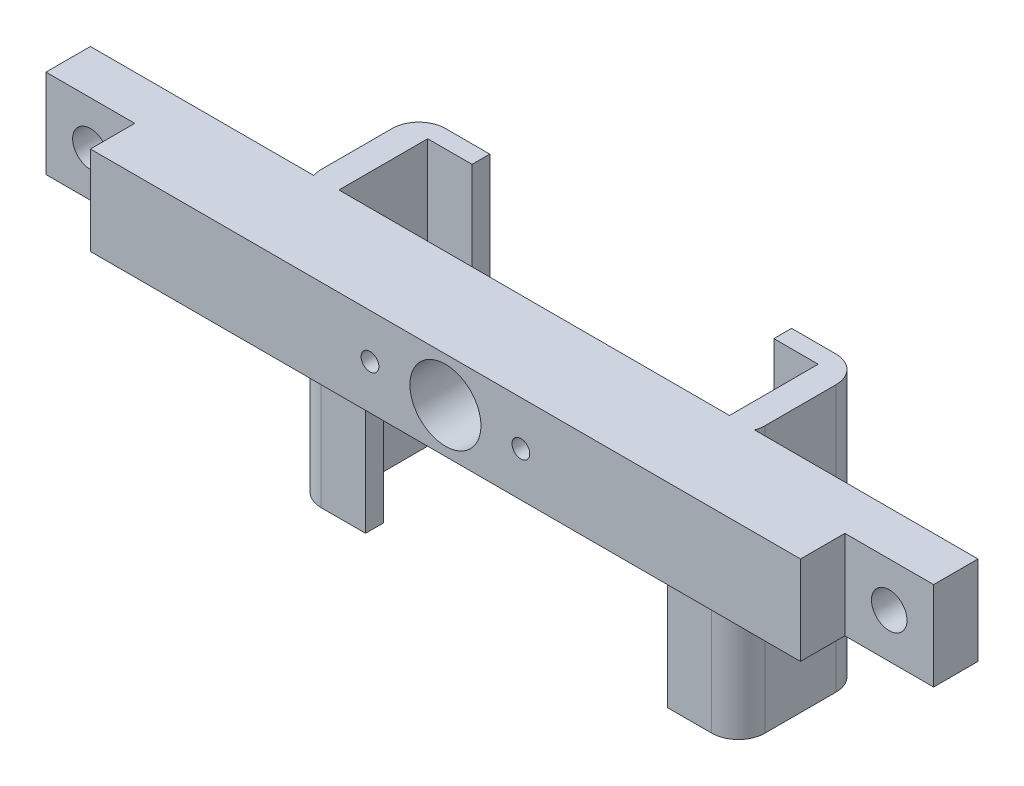
SolidWorks part; units mm, degrees
ref_plane "Front Plane" through (0, 0, 0) normal (0, 0, 1) x (1, 0, 0)
ref_plane "Top Plane" through (0, 0, 0) normal (0, 1, 0) x (1, 0, 0)
ref_plane "Right Plane" through (0, 0, 0) normal (1, 0, 0) x (0, 0, -1)
sketch "Sketch1" plane through (0, 0, 0) normal (0, 0, 1) x (1, 0, 0)
  line L1 (-50, 5) -> (50, 5)
  line L2 (-50, 5) -> (-50, -5)
  line L3 (-50, -5) -> (50, -5)
  line L4 (50, 5) -> (50, -5)
  line L5 (-50, 5) -> (50, -5) construction
  line L6 (-50, -5) -> (50, 5) construction
  point P0 (0, 0)
  dimension "D1" = 100
  dimension "D2" = 10
extrude "Boss-Extrude1" add sketch "Sketch1" along normal blind 10
sketch "Sketch2" plane through (0, 5, 0) normal (0, 1, 0) x (1, 0, 0)
  line L5 (-50, -10) -> (-40, -10)
  line L6 (-50, -10) -> (-50, -5)
  line L7 (-50, -5) -> (-40, -5)
  line L8 (-40, -10) -> (-40, -5)
  dimension "D1" = 10
  dimension "D2" = 5
sketch "Sketch6" plane through (0, 0, 0) normal (0, 0, -1) x (-1, 0, 0)
  line L0 (0, 5) -> (0, -5) construction
  line L1 (-25, 5) -> (-25, -5)
  line L3 (-25, 5) -> (-22, 5)
  line L4 (-50, 5) -> (-50, -5)
  line L5 (-50, -5) -> (50, -5)
  line L6 (-50, 5) -> (-50, -5)
  line L7 (50, 5) -> (-50, 5)
  line L9 (-50, -5) -> (50, -5)
  line L11 (50, 5) -> (-50, 5)
  line L12 (-22, 5) -> (-22, -5)
  line L13 (-22, -5) -> (-25, -5)
  line L17 (50, -5) -> (50, 5)
  line L18 (50, -5) -> (50, 5)
  line M11 (-50, -5) -> (50, -5)
  line M13 (50, 5) -> (-50, 5)
  dimension "D2" = 25
  dimension "D3" = 3
  dimension "D1" = 0
extrude "Boss-Extrude2" add sketch "Sketch6" along normal blind 12 contours L12 L1 M13 M11 region at (23.5, 0, 0)
sketch "Sketch8" plane through (22, 0, 0) normal (-1, 0, 0) x (0, 0, 1)
  line L0 (-12, -5) -> (0, -5) construction
  line L1 (-12, 5) -> (-10, 5)
  line L2 (-12, 5) -> (-12, -5)
  line L3 (-12, -5) -> (-10, -5)
  line L4 (-10, 5) -> (-10, -5)
  dimension "D1" = 2
extrude "Boss-Extrude3" add sketch "Sketch8" along normal blind 5
sketch "Sketch9" plane through (0, -5, 0) normal (0, -1, 0) x (1, 0, 0)
  line L0 (17, -12) -> (17, 0) construction
  line L1 (-50, 0) -> (22, 0) construction
  line L2 (17, 0) -> (22, 0)
  line L4 (17, 0) -> (17, 2)
  line L5 (17, 2) -> (25, 2)
  line L6 (25, 0) -> (25, 2)
  line L7 (22, 0) -> (22, -10)
  line L8 (22, -10) -> (17, -10)
  line L9 (17, -10) -> (17, -12)
  line L10 (17, -12) -> (25, -12)
  line L11 (25, -12) -> (25, 0)
  line L12 (25, 0) -> (25, 2)
  line L13 (-50, 10) -> (-50, 0) construction
  line L14 (-50, 10) -> (50, 10) construction
  line M16 (-50, 0) -> (22, 0)
  line M17 (22, 0) -> (22, -10)
  line M18 (22, -10) -> (17, -10)
  line M19 (17, -10) -> (17, -12)
  line M20 (17, -12) -> (25, -12)
  line M21 (25, -12) -> (25, 0)
  dimension "D1" = 8
  dimension "D2" = 2
  dimension "D3" = 2
extrude "Boss-Extrude4" add sketch "Sketch9" along normal blind 20 contours L6 L5 L4 M21 M16 M17 M18 M19 M20 region at (22.2097, -5, -5)
mirror "Mirror3" about plane through (0, 0, 0) normal (1, 0, 0) of "Boss-Extrude4", "Boss-Extrude3", "Boss-Extrude2"
extrude "Cut-Extrude1" cut sketch "Sketch2" against normal blind 10
mirror "Mirror4" about plane through (0, 0, 0) normal (1, 0, 0) of "Cut-Extrude1"
sketch "Sketch10" plane through (0, 0, 5) normal (0, 0, 1) x (1, 0, 0)
  line L0 (50, -5) -> (50, 5) construction
  line L1 (40, -5) -> (50, -5) construction
  circle A0 centre (45, 0) radius 2
  dimension "D1" = 4
  dimension "D2" = 5
  dimension "D3" = 5
extrude "Cut-Extrude2" cut sketch "Sketch10" against normal up to next
mirror "Mirror5" about plane through (0, 0, 0) normal (1, 0, 0) of "Cut-Extrude2"
sketch "Sketch12" plane through (0, 0, 0) normal (0, 0, -1) x (-1, 0, 0)
  line L0 (0, 5) -> (0, -5) construction
  line L1 (-22, 5) -> (22, 5) construction
  line L2 (17, -5) -> (-17, -5) construction
sketch "Sketch13" plane through (0, 0, 0) normal (0, 0, -1) x (-1, 0, 0)
  line L0 (0, 0) -> (-8.5, 0) construction
  line L1 (0, 0) -> (8.5, 0) construction
  circle A0 centre (0, 0) radius 4
  circle A1 centre (-8.5, 0) radius 1
  circle A2 centre (8.5, 0) radius 1
  dimension "D1" = 8
  dimension "D4" = 2
  dimension "D5" = 2
  dimension "D2" = 8.5
  dimension "D3" = 8.5
extrude "Cut-Extrude3" cut sketch "Sketch13" against normal through all
fillet "Fillet1" radius 3 2 edges at (25, -10, -12) (-25, -10, -12)
fillet "Fillet2" radius 3 2 edges at (-25, -15, 2) (25, -15, 2)
